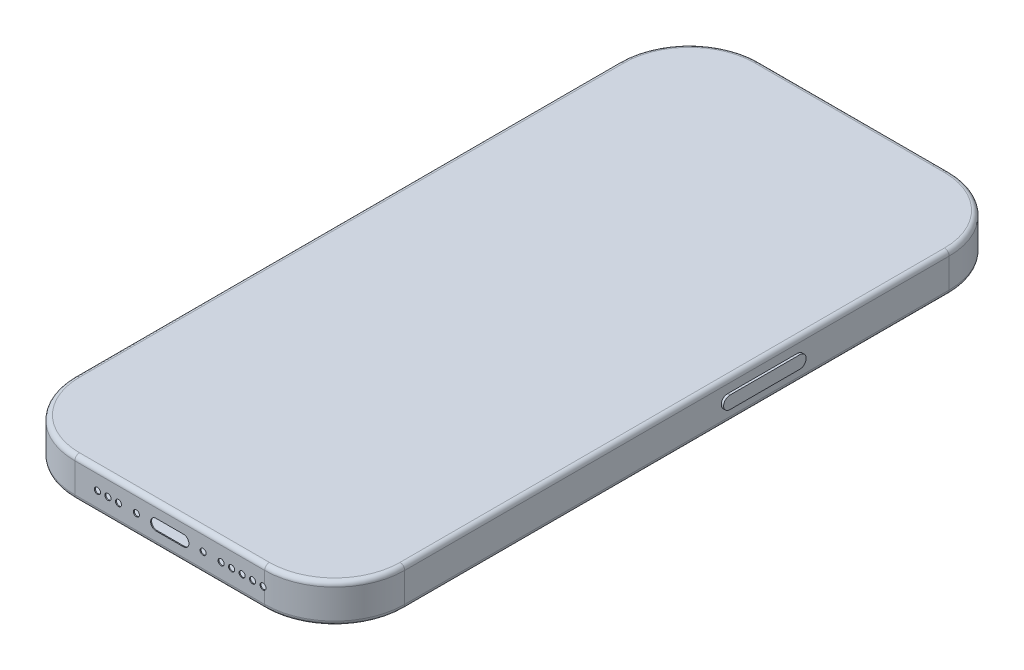
SolidWorks part; units mm, degrees
note: The reader was unsure of these and kept them because the rebuilt part matched: shared geometry of "Sketch23<2>".
other "Case"
other "Bezel"
material "AISI 316 Annealed Stainless Steel Bar (SS)"
ref_plane "Front Plane" through (0, 0, 0) normal (0, 0, 1) x (1, 0, 0)
ref_plane "Top Plane" through (0, 0, 0) normal (0, 1, 0) x (1, 0, 0)
ref_plane "Right Plane" through (0, 0, 0) normal (1, 0, 0) x (0, 0, -1)
ref_plane "Plane Right" through (33.8, 0, 0) normal (1, 0, 0) x (0, 0, -1)
ref_plane "Plane Left" through (-33.8, 0, 0) normal (1, 0, 0) x (0, 0, -1)
ref_plane "Button Plane" through (0, 3.5, 0) normal (0, 1, 0) x (-1, 0, 0)
sketch "Sketch1" plane through (0, 0, 0) normal (0, 1, 0) x (1, 0, 0)
  line L1 (-35.35, 0) -> (35.35, 0)
  line L2 (-35.35, 0) -> (-35.35, 146.7)
  line L3 (-35.35, 146.7) -> (35.35, 146.7)
  line L4 (35.35, 0) -> (35.35, 146.7)
  dimension "D1" = 70.7
  dimension "D2" = 146.7
extrude "Boss-Extrude1" add sketch "Sketch1" along normal blind 8.3
fillet "Fillet1" radius 15 4 edges at (-35.35, 4.15, -146.7) (35.35, 4.15, -146.7) (35.35, 4.15, 0) (-35.35, 4.15, 0)
fillet "Fillet2" radius 1 16 edges at (-30.9566, 0, -4.3934) (0, 0, 0) (30.9566, 0, -4.3934) (35.35, 0, -73.35) (30.9566, 0, -142.3066) (0, 0, -146.7) (-30.9566, 0, -142.3066) (-35.35, 0, -73.35) (30.9566, 8.3, -142.3066) (35.35, 8.3, -73.35) (30.9566, 8.3, -4.3934) (0, 8.3, 0) (-30.9566, 8.3, -4.3934) (-35.35, 8.3, -73.35) (-30.9566, 8.3, -142.3066) (0, 8.3, -146.7)
sketch "Sketch5" [suppressed] plane through (0, 0, 0) normal (0, 0, 1) x (1, 0, 0)
  line L0 (-23.6, 7.4) -> (23.6, 7.4) construction
  line L1 (-33.6, 8.55) -> (33.6, 8.55)
  line L2 (-33.6, 8.55) -> (-33.6, 6.25)
  line L3 (-33.6, 6.25) -> (33.6, 6.25)
  line L4 (33.6, 8.55) -> (33.6, 6.25)
  line L5 (-33.6, 8.55) -> (33.6, 6.25) construction
  line L6 (-33.6, 6.25) -> (33.6, 8.55) construction
  line L7 (38.885, 0) -> (-38.885, 0) construction
  arc A0 (-29.9, 7.4) -> (-29.9, 0) centre (-29.9, 3.7) ccw construction
  point P0 (0, 7.4)
  dimension "D1" = 6.25
sketch "Sketch3" plane through (0, 8.3, 0) normal (0, 1, 0) x (1, 0, 0)
  line L0 (0, -4.565) -> (0, 4.565) construction
  circle A0 centre (0, 9) radius 5
  dimension "D1" = 10
  dimension "D2" = 9
extrude "Button" [suppressed] cut sketch "Sketch3" against normal blind 0.5
chamfer "Button Chamfer" [suppressed] distance 0.5 angle 45
shell "Shell1" thickness 0.2
ref_plane "Plane1" through (0, 8.3, 0) normal (0, -1, 0) x (1, 0, 0)
sketch "Sketch21" plane through (0, 8.3, 0) normal (0, -1, 0) x (1, 0, 0)
  line L4 (20.35, -1) -> (-20.35, -1)
  line L5 (34.35, -131.7) -> (34.35, -15)
  line L6 (-20.35, -145.7) -> (20.35, -145.7)
  line L7 (-34.35, -15) -> (-34.35, -131.7)
  line L8 (20.35, -1) -> (-20.35, -1)
  line L9 (34.35, -131.7) -> (34.35, -15)
  line L10 (-20.35, -145.7) -> (20.35, -145.7)
  line L11 (-34.35, -15) -> (-34.35, -131.7)
  arc A4 (34.35, -15) -> (20.35, -1) centre (20.35, -15) ccw
  arc A5 (20.35, -145.7) -> (34.35, -131.7) centre (20.35, -131.7) ccw
  arc A6 (-34.35, -131.7) -> (-20.35, -145.7) centre (-20.35, -131.7) ccw
  arc A7 (-20.35, -1) -> (-34.35, -15) centre (-20.35, -15) ccw
  arc A8 (34.35, -15) -> (20.35, -1) centre (20.35, -15) ccw
  arc A9 (20.35, -145.7) -> (34.35, -131.7) centre (20.35, -131.7) ccw
  arc A10 (-34.35, -131.7) -> (-20.35, -145.7) centre (-20.35, -131.7) ccw
  arc A11 (-20.35, -1) -> (-34.35, -15) centre (-20.35, -15) ccw
  dimension "D1" = 0
extrude "Boss-Extrude6" add sketch "Sketch21" along normal blind 0.2 separate body
sketch "Sketch4" plane through (0, 8.3, 0) normal (0, 0, -1) x (1, 0, 0)
  line L1 (-20.35, 0) -> (20.35, 0) construction
  line L2 (0, 0) -> (0, 8.3) construction
  line L4 (20.35, 8.3) -> (-20.35, 8.3) construction
  circle A0 centre (11, 4.15) radius 0.65
  circle A1 centre (11, 4.15) radius 4.15 construction
  circle A2 centre (13.25, 4.15) radius 0.65
  circle A3 centre (15.5, 4.15) radius 0.65
  circle A4 centre (17.75, 4.15) radius 0.65
  circle A5 centre (20, 4.15) radius 0.65
  circle A6 centre (-11, 4.15) radius 0.65
  circle A7 centre (-13.25, 4.15) radius 0.65
  circle A8 centre (-15.5, 4.15) radius 0.65
  dimension "D1" = 1.3
  dimension "D4" = 9
  dimension "D5" = 2.25
  dimension "D7" = 2.25
  dimension "D2" = 22
  dimension "D3" = 5
  dimension "D6" = 3
extrude "Speakers" cut sketch "Sketch4" along normal up to next
sketch "Sketch19" plane through (0, 0, 0) normal (0, 0, 1) x (1, 0, 0)
  line L0 (0, 0) -> (0, 8.3) construction
  line L1 (-20.35, 8.3) -> (20.35, 8.3) construction
  line L2 (-7.15, 4.15) -> (7.15, 4.15) construction
  circle A0 centre (-7.15, 4.15) radius 0.65
  circle A1 centre (7.15, 4.15) radius 0.65
  circle A2 centre (11, 4.15) radius 0.65 construction
  point P10 (0, 4.15)
  dimension "D1" = 14.3
extrude "Microphones" cut sketch "Sketch19" against normal up to next (0.2 mm away)
sketch "Sketch20" plane through (0, 0, 0) normal (0, 0, 1) x (1, 0, 0)
  line L0 (-2.925, 4.15) -> (2.925, 4.15) construction
  line L1 (-2.925, 5.325) -> (2.925, 5.325)
  line L2 (-2.925, 2.975) -> (2.925, 2.975)
  line L3 (0, 0) -> (0, 8.3) construction
  line L4 (-20.35, 8.3) -> (20.35, 8.3) construction
  arc A0 (-2.925, 5.325) -> (-2.925, 2.975) centre (-2.925, 4.15) ccw
  arc A1 (2.925, 2.975) -> (2.925, 5.325) centre (2.925, 4.15) ccw
  point P2 (0, 4.15)
  dimension "D1" = 2.35
  dimension "D2" = 8.2
extrude "USB-C" cut sketch "Sketch20" against normal up to next (0.2 mm away)
sketch "Sketch7" plane through (0, 0, 0) normal (0, -1, 0) x (1, 0, 0)
  line L2 (35.15, -15) -> (35.15, -131.7) construction
  line L3 (22.45, -142.8) -> (1.15, -142.8)
  line L4 (32.45, -132.8) -> (32.45, -111.5)
  line L5 (22.45, -101.5) -> (1.15, -101.5)
  line L6 (-8.85, -132.8) -> (-8.85, -111.5)
  line L7 (32.45, -142.8) -> (-8.85, -101.5) construction
  line L8 (32.45, -101.5) -> (-8.85, -142.8) construction
  line L9 (20.35, -146.5) -> (-20.35, -146.5) construction
  arc A0 (1.15, -142.8) -> (-8.85, -132.8) centre (1.15, -132.8) cw
  arc A1 (1.15, -101.5) -> (-8.85, -111.5) centre (1.15, -111.5) ccw
  arc A2 (32.45, -111.5) -> (22.45, -101.5) centre (22.45, -111.5) ccw
  arc A3 (22.45, -142.8) -> (32.45, -132.8) centre (22.45, -132.8) ccw
  point P0 (11.8, -122.15)
  dimension "D1" = 41.3
  dimension "D2" = 44
  dimension "D3" = 45
  dimension "D4" = 10
extrude "Camera Rear" add sketch "Sketch7" along normal blind 2
chamfer "Chamfer1" distance 2 angle 45 8 edges at (-8.85, -2, -122.15) (-5.9211, -2, -104.4289) (11.8, -2, -101.5) (29.5211, -2, -104.4289) (32.45, -2, -122.15) (29.5211, -2, -139.8711) (11.8, -2, -142.8) (-5.9211, -2, -139.8711)
sketch "Sketch22" plane through (0, -2, 0) normal (0, -1, 0) x (1, 0, 0)
  line L0 (20.8, -131.15) -> (20.8, -113.15) construction
  line L1 (20.8, -113.15) -> (2.8, -122.15) construction
  line L2 (2.8, -122.15) -> (20.8, -131.15) construction
  line L3 (-6.85, -111.5) -> (-6.85, -132.8) construction
  line L4 (1.15, -140.8) -> (22.45, -140.8) construction
  line L5 (30.45, -132.8) -> (30.45, -111.5) construction
  line L6 (22.45, -103.5) -> (1.15, -103.5) construction
  circle A0 centre (20.8, -131.15) radius 8.1
  circle A1 centre (20.8, -113.15) radius 8.1
  circle A2 centre (2.8, -122.15) radius 8.1
  circle A3 centre (20.8, -131.15) radius 9.65 construction
  circle A4 centre (20.8, -113.15) radius 9.65 construction
  circle A5 centre (2.8, -122.15) radius 9.65 construction
  dimension "D1" = 16.2
  dimension "D3" = 1.8
  dimension "D4" = 34.2
  dimension "D2" = 1.55
extrude "Cut-Extrude5" cut sketch "Sketch22" against normal up to surface (2 mm away) up to face at (0, 0, -73.35)
sketch "Sketch23" plane through (0, 0, 0) normal (0, -1, 0) x (1, 0, 0)
  circle A0 centre (20.8, -131.15) radius 8.1 construction
  circle A1 centre (20.8, -113.15) radius 8.1 construction
  circle A2 centre (2.8, -122.15) radius 8.1 construction
  circle A3 centre (20.8, -131.15) radius 8.1
  circle A4 centre (20.8, -113.15) radius 8.1
  circle A5 centre (2.8, -122.15) radius 8.1
  circle A6 centre (2.8, -122.15) radius 6.6
  circle A7 centre (20.8, -113.15) radius 6.6
  circle A8 centre (20.8, -131.15) radius 6.6
  dimension "D1" = 1.5
extrude "Boss-Extrude7" add sketch "Sketch23" along normal offset from surface (3.75 mm away) 1.75 separate body up to face at (2.8, -2, -130.25) offset beyond the face yes
extrude "Boss-Extrude8" add sketch "Sketch23<2>" along normal up to surface (3.75 mm away) separate body contours A8 | A7 | A6 up to face at (20.8, -3.75, -124.55)
sketch "Sketch23<2>" plane through (0, 0, 0) normal (0, -1, 0) x (1, 0, 0) same geometry as "Sketch23"
sketch "Sketch24" plane through (0, -2, 0) normal (0, -1, 0) x (1, 0, 0)
  line L0 (10.9, -122.15) -> (-5.3, -122.15) construction
  line L1 (2.8, -135.65) -> (2.8, -108.65) construction
  circle A0 centre (2.8, -135.65) radius 3.5
  circle A1 centre (2.8, -122.15) radius 8.1 construction
  circle A2 centre (2.8, -108.65) radius 3.5
  point P6 (2.8, -122.15)
  dimension "D1" = 7
  dimension "D2" = 27
split line "Split Line7"
sketch "Sketch11" plane through (35.35, 0, 0) normal (1, 0, 0) x (0, 0, -1)
  line L0 (84.2, 4.15) -> (99.2, 4.15) construction
  line L1 (84.2, 5.5) -> (99.2, 5.5)
  line L2 (84.2, 2.8) -> (99.2, 2.8)
  line L3 (131.7, 1) -> (131.7, 7.3) construction
  line L6 (131.7, 0) -> (15, 0) construction
  line L7 (131.7, 8.3) -> (15, 8.3) construction
  arc A0 (84.2, 5.5) -> (84.2, 2.8) centre (84.2, 4.15) ccw
  arc A1 (99.2, 2.8) -> (99.2, 5.5) centre (99.2, 4.15) ccw
  circle A2 centre (91.7, 4.15) radius 4.15 construction
  point P2 (91.7, 4.15)
  dimension "D1" = 17.7
  dimension "D2" = 2.7
  dimension "D3" = 40
extrude "Button A" add sketch "Sketch11" along normal blind 0.5
sketch "Sketch14" plane through (-35.35, 0, 0) normal (1, 0, 0) x (0, 0, -1)
  line L0 (106.95, 4.15) -> (98.45, 4.15) construction
  line L1 (106.95, 2.8) -> (98.45, 2.8)
  line L2 (106.95, 5.5) -> (98.45, 5.5)
  line L3 (95.7, 0) -> (95.7, 8.3) construction
  line L4 (131.7, 7.3) -> (131.7, 1) construction
  line L7 (84.45, 4.15) -> (92.95, 4.15) construction
  line L8 (84.45, 2.8) -> (92.95, 2.8)
  line L9 (84.45, 5.5) -> (92.95, 5.5)
  line L11 (15, 0) -> (131.7, 0) construction
  line L12 (15, 8.3) -> (131.7, 8.3) construction
  arc A0 (106.95, 2.8) -> (106.95, 5.5) centre (106.95, 4.15) ccw
  arc A1 (98.45, 5.5) -> (98.45, 2.8) centre (98.45, 4.15) ccw
  arc A2 (84.45, 2.8) -> (84.45, 5.5) centre (84.45, 4.15) cw
  arc A3 (92.95, 5.5) -> (92.95, 2.8) centre (92.95, 4.15) cw
  point P2 (102.7, 4.15)
  point P11 (95.7, 4.15)
  point P17 (88.7, 4.15)
  dimension "D2" = 2.7
  dimension "D3" = 11.2
  dimension "D1" = 25.2
  dimension "D4" = 14
  dimension "D5" = 36
extrude "Button B & C" add sketch "Sketch14" against normal blind 0.5
sketch "Sketch15" plane through (-35.35, 0, 0) normal (1, 0, 0) x (0, 0, -1)
  line L0 (118.1, 4.15) -> (115.3, 4.15) construction
  line L1 (118.1, 2.8) -> (115.3, 2.8)
  line L2 (118.1, 5.5) -> (115.3, 5.5)
  line L4 (106.95, 5.5) -> (98.45, 5.5) construction
  line L5 (98.45, 2.8) -> (106.95, 2.8) construction
  arc A0 (118.1, 2.8) -> (118.1, 5.5) centre (118.1, 4.15) ccw
  arc A1 (115.3, 5.5) -> (115.3, 2.8) centre (115.3, 4.15) ccw
  point P2 (116.7, 4.15)
  point P7 (102.7, 2.8)
  dimension "D2" = 5.5
  dimension "D3" = 14
  dimension "D1" = 2.7
extrude "Button D" add sketch "Sketch15" against normal up to surface (0.5 mm away) up to face at (-35.85, 4.15, -102.7)
equation "\"D7@Sketch4\" = \"D5@Sketch4\""
